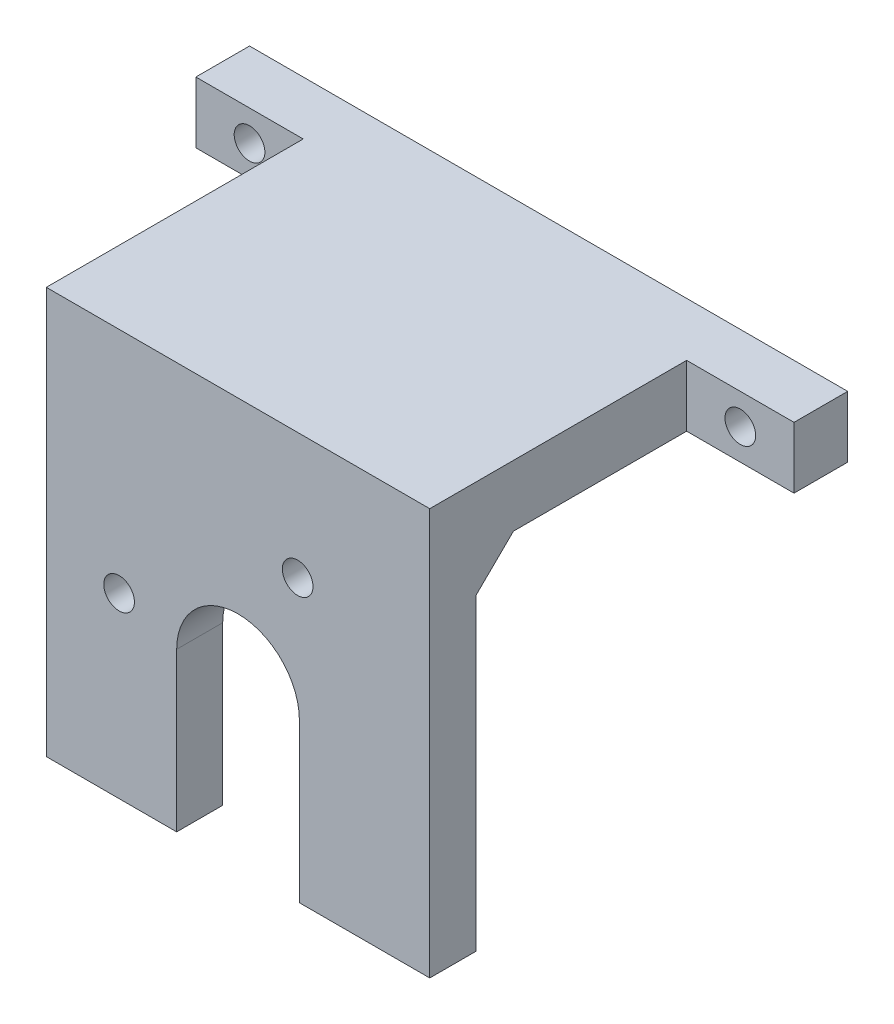
SolidWorks part; units mm, degrees
material "ABS"
ref_plane "Front Plane" through (0, 0, 0) normal (0, 0, 1) x (1, 0, 0)
ref_plane "Top Plane" through (0, 0, 0) normal (0, 1, 0) x (1, 0, 0)
ref_plane "Right Plane" through (0, 0, 0) normal (1, 0, 0) x (0, 0, -1)
sketch "Sketch1" plane through (0, 0, 0) normal (0, 0, 1) x (1, 0, 0)
  line L1 (-37.3941, 10.9555) -> (12.6059, 10.9555)
  line L2 (-37.3941, 10.9555) -> (-37.3941, -7.0445)
  line L3 (-37.3941, -7.0445) -> (12.6059, -7.0445)
  line L4 (12.6059, 10.9555) -> (12.6059, -7.0445)
  dimension "D1" = 50
  dimension "D2" = 18
extrude "Boss-Extrude1" add sketch "Sketch1" along normal blind 7
sketch "Sketch2" plane through (0, 0, 7) normal (0, 0, 1) x (1, 0, 0)
  line L0 (12.6059, -7.0445) -> (12.6059, 10.9555) construction
  line L1 (-37.3941, 10.9555) -> (12.6059, 10.9555)
  line L2 (-37.3941, 10.9555) -> (-37.3941, 2.9555)
  line L3 (-37.3941, 2.9555) -> (12.6059, 2.9555)
  line L4 (12.6059, 10.9555) -> (12.6059, 2.9555)
  dimension "D1" = 8
extrude "Boss-Extrude2" add sketch "Sketch2" along normal blind 33.5
sketch "Sketch3" plane through (12.6059, 0, 0) normal (1, 0, 0) x (0, 0, -1)
  line L0 (-40.5, 10.9555) -> (0, 10.9555) construction
  line L1 (-7, 2.9555) -> (0, 2.9555)
  line L2 (-7, 2.9555) -> (-7, 10.9555)
  line L3 (-7, 10.9555) -> (0, 10.9555)
  line L4 (0, 2.9555) -> (0, 10.9555)
extrude "Boss-Extrude3" add sketch "Sketch3" along normal blind 14
sketch "Sketch4" plane through (-37.3941, 0, 0) normal (-1, 0, 0) x (0, 0, 1)
  line L1 (7, 2.9555) -> (0, 2.9555)
  line L2 (7, 2.9555) -> (7, 10.9555)
  line L3 (7, 10.9555) -> (0, 10.9555)
  line L4 (0, 2.9555) -> (0, 10.9555)
extrude "Boss-Extrude4" add sketch "Sketch4" along normal blind 14
sketch "Sketch5" plane through (0, 0, 7) normal (0, 0, 1) x (1, 0, 0)
  line L1 (-37.3941, -7.0445) -> (12.6059, -7.0445)
  line L2 (-37.3941, -7.0445) -> (-37.3941, 2.9555)
  line L3 (-37.3941, 2.9555) -> (12.6059, 2.9555)
  line L4 (12.6059, -7.0445) -> (12.6059, 2.9555)
extrude "Cut-Extrude1" cut sketch "Sketch5" against normal blind 14
sketch "Sketch6" plane through (0, 0, 7) normal (0, 0, 1) x (1, 0, 0)
  line L0 (26.6059, 10.9555) -> (26.6059, 2.9555) construction
  line L1 (-51.3941, 2.9555) -> (-51.3941, 10.9555) construction
  line L2 (-51.3941, 2.9555) -> (-37.3941, 2.9555) construction
  line L3 (26.6059, 2.9555) -> (12.6059, 2.9555) construction
  circle A0 centre (-44.3941, 6.9555) radius 2
  circle A1 centre (19.6059, 6.9555) radius 2
  dimension "D1" = 4
  dimension "D2" = 4
  dimension "D3" = 7
  dimension "D4" = 7
  dimension "D5" = 4
  dimension "D6" = 4
extrude "Cut-Extrude2" cut sketch "Sketch6" against normal blind 14
sketch "Sketch7" plane through (0, 2.9555, 0) normal (0, -1, 0) x (1, 0, 0)
  line L0 (12.6059, 40.5) -> (12.6059, 7) construction
  line L1 (-37.3941, 40.5) -> (12.6059, 40.5)
  line L2 (-37.3941, 40.5) -> (-37.3941, 34.5)
  line L3 (-37.3941, 34.5) -> (12.6059, 34.5)
  line L4 (12.6059, 40.5) -> (12.6059, 34.5)
  dimension "D1" = 6
extrude "Boss-Extrude5" add sketch "Sketch7" along normal blind 45
sketch "Sketch8" plane through (0, 0, 40.5) normal (0, 0, 1) x (1, 0, 0)
  line L0 (-12.3941, -21.4212) -> (-12.3941, -42.0445) construction
  line L1 (12.6059, -42.0445) -> (-37.3941, -42.0445) construction
  line L2 (-4.3941, -21.4212) -> (-4.3941, -42.0445)
  line L3 (-20.3941, -21.4212) -> (-20.3941, -42.0445)
  line L4 (-37.3941, 10.9555) -> (-37.3941, -42.0445) construction
  arc A0 (-4.3941, -21.4212) -> (-20.3941, -21.4212) centre (-12.3941, -21.4212) ccw
  arc A1 (-20.3941, -42.0445) -> (-4.3941, -42.0445) centre (-12.3941, -42.0445) ccw
  point P4 (-12.3941, -31.7328)
  dimension "D1" = 16
  dimension "D2" = 25
extrude "Cut-Extrude3" cut sketch "Sketch8" against normal blind 35
sketch "Sketch9" plane through (0, 0, 34.5) normal (0, 0, -1) x (-1, 0, 0)
  circle A0 centre (27.901, -18.8469) radius 2
  circle A1 centre (4.6167, -5.4607) radius 2
  dimension "D1" = 4
  dimension "D2" = 4
extrude "Cut-Extrude5" cut sketch "Sketch9" against normal blind 35
sketch "Sketch12" plane through (-37.3941, 0, 0) normal (-1, 0, 0) x (0, 0, 1)
  line L0 (34.5, -1.8735) -> (29.5873, 2.9555)
  line L1 (34.5, -42.0445) -> (34.5, 2.9555) construction
  line L2 (34.5, 2.9555) -> (7, 2.9555) construction
  line L3 (29.5873, 2.9555) -> (34.5, 2.9555)
  line L4 (34.5, 2.9555) -> (34.5, -1.8735)
extrude "Boss-Extrude8" add sketch "Sketch12" against normal blind 50
